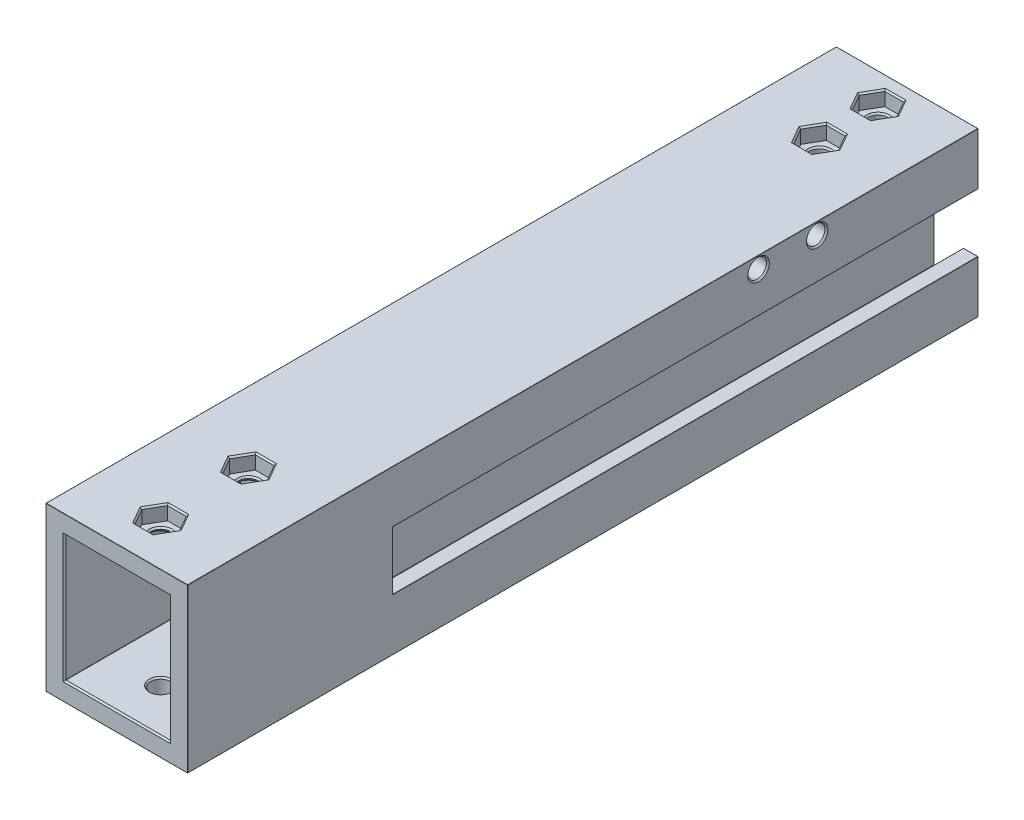
SolidWorks part; units mm, degrees
ref_plane "Front Plane" through (0, 0, 0) normal (0, 0, 1) x (1, 0, 0)
ref_plane "Top Plane" through (0, 0, 0) normal (0, 1, 0) x (1, 0, 0)
ref_plane "Right Plane" through (0, 0, 0) normal (1, 0, 0) x (0, 0, -1)
sketch "Sketch1" plane through (0, 0, 0) normal (0, 0, 1) x (1, 0, 0)
  line L0 (-6.35, -6.35) -> (-6.35, 49.35)
  line L1 (0, 0) -> (35.72, 0) construction
  line L2 (0, 0) -> (0, 43) construction
  line L3 (0, 43) -> (35.72, 43) construction
  line L4 (35.72, 0) -> (35.72, 43) construction
  line L5 (-6.35, 49.35) -> (42.07, 49.35)
  line L6 (42.07, -6.35) -> (42.07, 49.35)
  line L7 (-6.35, -6.35) -> (42.07, -6.35)
  dimension "D1" = 35.72
  dimension "D2" = 43
  dimension "D3" = 6.35
extrude "Boss-Extrude1" add sketch "Sketch1" against normal blind 270
sketch "Sketch2" plane through (0, 0, 0) normal (0, 0, 1) x (1, 0, 0)
  line L0 (35.72, 43) -> (0, 43)
  line L1 (0, 43) -> (0, 0)
  line L2 (0, 0) -> (35.72, 0)
  line L3 (35.72, 0) -> (35.72, 43)
  line L4 (-6.35, -6.35) -> (42.07, -6.35)
  line L5 (42.07, -6.35) -> (42.07, 49.35)
  line L6 (42.07, 49.35) -> (-6.35, 49.35)
  line L7 (-6.35, 49.35) -> (-6.35, -6.35)
  line L8 (-6.35, -6.35) -> (42.07, -6.35) construction
  line L9 (42.07, -6.35) -> (42.07, 49.35) construction
  line L10 (42.07, 49.35) -> (-6.35, 49.35) construction
  line L11 (-6.35, 49.35) -> (-6.35, -6.35) construction
  dimension "D1" = 0
  dimension "D2" = 6.35
extrude "Cut-Extrude1" cut sketch "Sketch2" against normal blind 60
sketch "Sketch3" plane through (0, -6.35, 0) normal (0, -1, 0) x (1, 0, 0)
  line L4 (42.07, 0) -> (-6.35, 0)
  line L5 (-6.35, 0) -> (-6.35, -270)
  line L12 (-6.35, -270) -> (42.07, -270)
  line L13 (42.07, -270) -> (42.07, 0)
  line L14 (42.07, 0) -> (-6.35, 0) construction
  line L15 (-6.35, 0) -> (-6.35, -270) construction
  line L16 (-6.35, -270) -> (42.07, -270) construction
  line L17 (42.07, -270) -> (42.07, 0) construction
  circle A1 centre (17.86, -260) radius 3.3734
  circle A3 centre (17.86, -240) radius 3.3734
  circle A5 centre (17.86, -45) radius 3.3734
  circle A8 centre (17.86, -15) radius 3.3734
  point P3 (17.86, -270)
  point P12 (0, 0)
  dimension "D6" = 6.7469
  dimension "D2" = 10
  dimension "D3" = 20
  dimension "D4" = 15
  dimension "D5" = 30
  dimension "D1" = 0
extrude "Cut-Extrude2" cut sketch "Sketch3" against normal through all
sketch "Sketch8" plane through (0, 0, -270) normal (0, 0, -1) x (-1, 0, 0)
  line L0 (6.35, 21.5) -> (-42.07, 21.5) construction
  line L1 (6.35, 11.5) -> (1.35, 11.5)
  line L2 (1.35, 11.5) -> (1.35, 1.5)
  line L3 (1.35, 1.5) -> (-8.65, 1.5)
  line L4 (-42.07, -6.35) -> (6.35, -6.35)
  line L5 (6.35, -6.35) -> (6.35, 49.35)
  line L6 (6.35, 49.35) -> (-42.07, 49.35)
  line L7 (-42.07, 49.35) -> (-42.07, -6.35)
  line L8 (-42.07, -6.35) -> (6.35, -6.35) construction
  line L9 (6.35, -6.35) -> (6.35, 49.35) construction
  line L10 (6.35, 49.35) -> (-42.07, 49.35) construction
  line L11 (-42.07, 49.35) -> (-42.07, -6.35) construction
  line L12 (-8.65, 1.5) -> (-8.65, 41.5)
  line L13 (6.35, 31.5) -> (1.35, 31.5)
  line L14 (1.35, 31.5) -> (1.35, 41.5)
  line L15 (1.35, 41.5) -> (-8.65, 41.5)
  line L16 (-17.86, -6.35) -> (-17.86, 49.35) construction
  line L17 (-42.07, 11.5) -> (-37.07, 11.5)
  line L18 (-37.07, 11.5) -> (-37.07, 1.5)
  line L19 (-37.07, 1.5) -> (-27.07, 1.5)
  line L20 (-42.07, 31.5) -> (-37.07, 31.5)
  line L21 (-37.07, 41.5) -> (-27.07, 41.5)
  line L22 (-37.07, 31.5) -> (-37.07, 41.5)
  line L23 (-27.07, 1.5) -> (-27.07, 41.5)
  line L24 (6.35, 31.5) -> (6.35, 11.5)
  line L25 (-42.07, 31.5) -> (-42.07, 11.5)
  point P2 (6.35, 21.5)
  point P16 (-8.65, 21.5)
  dimension "D2" = 10
  dimension "D3" = 20
  dimension "D4" = 10
  dimension "D5" = 5
  dimension "D1" = 0
extrude "Cut-Extrude4" cut sketch "Sketch8" against normal blind 200
sketch "Sketch11" plane through (-6.35, 0, 0) normal (-1, 0, 0) x (0, 0, 1)
  circle A0 centre (-195, 45.2313) radius 3.175 construction
  circle A1 centre (-215, 45.2313) radius 3.175 construction
  circle A2 centre (-195, 45.2313) radius 3.175
  circle A3 centre (-215, 45.2313) radius 3.175
extrude "Cut-Extrude5" cut sketch "Sketch11" against normal through all
sketch "Sketch12" plane through (0, 0, -270) normal (0, 0, -1) x (-1, 0, 0)
  line L0 (-42.07, 31.5) -> (-42.07, 11.5) construction
  line L1 (-10.36, 6.5) -> (-25.36, 6.5)
  line L2 (-10.36, 6.5) -> (-10.36, 36.5)
  line L3 (-10.36, 36.5) -> (-25.36, 36.5)
  line L4 (-25.36, 6.5) -> (-25.36, 36.5)
  line L20 (6.35, -6.35) -> (6.35, 11.5)
  line L21 (6.35, 11.5) -> (1.35, 11.5)
  line L22 (1.35, 11.5) -> (1.35, 1.5)
  line L23 (1.35, 1.5) -> (-8.65, 1.5)
  line L24 (-8.65, 1.5) -> (-8.65, 41.5)
  line L25 (-8.65, 41.5) -> (1.35, 41.5)
  line L26 (1.35, 41.5) -> (1.35, 31.5)
  line L27 (1.35, 31.5) -> (6.35, 31.5)
  line L28 (6.35, 31.5) -> (6.35, 49.35)
  line L29 (6.35, 49.35) -> (-42.07, 49.35)
  line L30 (-42.07, 49.35) -> (-42.07, 31.5)
  line L31 (-42.07, 31.5) -> (-37.07, 31.5)
  line L32 (-37.07, 31.5) -> (-37.07, 41.5)
  line L33 (-37.07, 41.5) -> (-27.07, 41.5)
  line L34 (-27.07, 41.5) -> (-27.07, 1.5)
  line L35 (-27.07, 1.5) -> (-37.07, 1.5)
  line L36 (-37.07, 1.5) -> (-37.07, 11.5)
  line L37 (-37.07, 11.5) -> (-42.07, 11.5)
  line L38 (-42.07, 11.5) -> (-42.07, -6.35)
  line L39 (-42.07, -6.35) -> (6.35, -6.35)
  line L40 (6.35, -6.35) -> (6.35, 11.5) construction
  line L41 (6.35, 11.5) -> (1.35, 11.5) construction
  line L42 (1.35, 11.5) -> (1.35, 1.5) construction
  line L43 (1.35, 1.5) -> (-8.65, 1.5) construction
  line L44 (-8.65, 1.5) -> (-8.65, 41.5) construction
  line L45 (-8.65, 41.5) -> (1.35, 41.5) construction
  line L46 (1.35, 41.5) -> (1.35, 31.5) construction
  line L47 (1.35, 31.5) -> (6.35, 31.5) construction
  line L48 (6.35, 31.5) -> (6.35, 49.35) construction
  line L49 (6.35, 49.35) -> (-42.07, 49.35) construction
  line L50 (-42.07, 49.35) -> (-42.07, 31.5) construction
  line L51 (-42.07, 31.5) -> (-37.07, 31.5) construction
  line L52 (-37.07, 31.5) -> (-37.07, 41.5) construction
  line L53 (-37.07, 41.5) -> (-27.07, 41.5) construction
  line L54 (-27.07, 41.5) -> (-27.07, 1.5) construction
  line L55 (-27.07, 1.5) -> (-37.07, 1.5) construction
  line L56 (-37.07, 1.5) -> (-37.07, 11.5) construction
  line L57 (-37.07, 11.5) -> (-42.07, 11.5) construction
  line L58 (-42.07, 11.5) -> (-42.07, -6.35) construction
  line L59 (-42.07, -6.35) -> (6.35, -6.35) construction
  point P10 (-25.36, 21.5)
  point P12 (-17.86, 6.5)
  point P14 (-42.07, 21.5)
  point P16 (-17.86, -6.35)
  dimension "D2" = 30
  dimension "D3" = 15
  dimension "D1" = 0
extrude "Cut-Extrude6" cut sketch "Sketch12" against normal blind 50
sketch "Sketch13" plane through (0, 49.35, 0) normal (0, 1, 0) x (1, 0, 0)
  line L1 (24.2758, 240) -> (21.0679, 245.5563)
  line L2 (21.0679, 245.5563) -> (14.6521, 245.5563)
  line L3 (14.6521, 245.5563) -> (11.4442, 240)
  line L4 (-6.35, 0) -> (42.07, 0)
  line L12 (11.4442, 240) -> (14.6521, 234.4437)
  line L13 (14.6521, 234.4437) -> (21.0679, 234.4437)
  line L14 (21.0679, 234.4437) -> (24.2758, 240)
  line L15 (24.2758, 260) -> (21.0679, 265.5563)
  line L16 (21.0679, 265.5563) -> (14.6521, 265.5562)
  line L17 (14.6521, 265.5562) -> (11.4442, 260)
  line L18 (11.4442, 260) -> (14.6521, 254.4438)
  line L19 (14.6521, 254.4438) -> (21.0679, 254.4438)
  line L20 (21.0679, 254.4438) -> (24.2758, 260)
  line L21 (24.2758, 45) -> (21.0679, 50.5563)
  line L22 (21.0679, 50.5563) -> (14.6521, 50.5563)
  line L23 (14.6521, 50.5563) -> (11.4442, 45)
  line L24 (11.4442, 45) -> (14.6521, 39.4438)
  line L25 (14.6521, 39.4438) -> (21.0679, 39.4438)
  line L26 (21.0679, 39.4438) -> (24.2758, 45)
  line L27 (24.2758, 15) -> (21.0679, 20.5563)
  line L28 (21.0679, 20.5563) -> (14.6521, 20.5563)
  line L29 (14.6521, 20.5563) -> (11.4442, 15)
  line L30 (11.4442, 15) -> (14.6521, 9.4437)
  line L31 (14.6521, 9.4437) -> (21.0679, 9.4438)
  line L32 (21.0679, 9.4438) -> (24.2758, 15)
  line L68 (-6.35, 0) -> (42.07, 0) construction
  line L72 (42.07, 0) -> (42.07, 270)
  line L74 (42.07, 0) -> (42.07, 270) construction
  line L76 (42.07, 270) -> (-6.35, 270)
  line L77 (42.07, 270) -> (-6.35, 270) construction
  line L78 (-6.35, 270) -> (-6.35, 0)
  line L79 (-6.35, 270) -> (-6.35, 0) construction
  circle A0 centre (17.86, 45) radius 3.3734 construction
  circle A2 centre (17.86, 260) radius 3.3734 construction
  circle A4 centre (17.86, 45) radius 3.3734 construction
  circle A6 centre (17.86, 260) radius 3.3734 construction
  circle A8 centre (17.86, 240) radius 5.5563 construction
  circle A9 centre (17.86, 260) radius 5.5563 construction
  circle A10 centre (17.86, 45) radius 5.5563 construction
  circle A11 centre (17.86, 15) radius 5.5562 construction
  circle A12 centre (17.86, 15) radius 3.3734 construction
  circle A13 centre (17.86, 240) radius 3.3734 construction
  circle A14 centre (17.86, 15) radius 3.3734 construction
  circle A15 centre (17.86, 240) radius 3.3734 construction
  point P0 (18.7361, 269.0167)
  point P5 (0, 0)
  point P7 (0, 0)
  point P11 (0, 0)
  point P12 (10.1894, 244.5739)
  point P16 (23.22, 15)
  point P17 (17.86, 234.4437)
  point P46 (17.86, 50.5563)
  point P47 (17.86, 9.4438)
  point P55 (0, 0)
  point P56 (12.5989, 260)
  dimension "D2" = 11.1125
  dimension "D3" = 11.1125
  dimension "D4" = 11.1125
  dimension "D5" = 11.1125
  dimension "D1" = 0
extrude "Cut-Extrude9" cut sketch "Sketch13" against normal blind 5
chamfer "Chamfer1" distance 0.5 angle 45 52 edges at (-6.35, 45.2313, -211.825) (42.07, 45.2313, -211.825) (-6.35, 45.2313, -191.825) (42.07, 45.2313, -191.825) (21.2334, 0, -45) (17.86, -6.35, -48.3734) (35.72, 21.5, 0) (17.86, 0, 0) (17.86, 43, 0) (0, 21.5, 0) (14.4866, 43, -45) (25.36, 21.5, -270) (17.86, 6.5, -270) (10.36, 21.5, -270) (17.86, 36.5, -270) (17.86, -6.35, -263.3734) (21.2334, 6.5, -260) (14.4866, 36.5, -260) (21.2334, 0, -15) (17.86, -6.35, -18.3734) (17.86, -6.35, -243.3734) (21.2334, 6.5, -240) (14.4866, 36.5, -240) (14.4866, 43, -15) (22.6719, 49.35, -242.7781) (22.6719, 49.35, -237.2219) (17.86, 49.35, -234.4437) (13.0481, 49.35, -237.2219) (13.0481, 49.35, -242.7781) (17.86, 49.35, -245.5563) (13.0481, 49.35, -257.2219) (17.86, 49.35, -254.4438) (22.6719, 49.35, -257.2219) (22.6719, 49.35, -262.7781) (17.86, 49.35, -265.5563) (13.0481, 49.35, -262.7781) (17.86, 44.35, -256.6266) (17.86, 44.35, -236.6266) (22.6719, 49.35, -17.7781) (22.6719, 49.35, -12.2219) (17.86, 49.35, -9.4438) (13.0481, 49.35, -12.2219) (13.0481, 49.35, -17.7781) (17.86, 49.35, -20.5563) (22.6719, 49.35, -42.2219) (22.6719, 49.35, -47.7781) (17.86, 49.35, -50.5563) (13.0481, 49.35, -47.7781) (17.86, 49.35, -39.4438) (13.0481, 49.35, -42.2219) (17.86, 44.35, -41.6266) (17.86, 44.35, -11.6266)
fillet "Fillet7" radius 0.1 76 edges at (42.07, 11.5, -170) (39.57, 11.5, -270) (32.07, 1.5, -270) (27.07, 1.5, -170) (27.07, 21.5, -270) (42.07, 31.5, -170) (39.57, 31.5, -270) (27.07, 41.5, -170) (32.07, 41.5, -270) (-1.35, 41.5, -170) (3.65, 41.5, -270) (-1.35, 1.5, -170) (3.65, 1.5, -270) (8.65, 41.5, -170) (8.65, 1.5, -170) (8.65, 21.5, -270) (17.86, 0, -60) (0, 21.5, -60) (17.86, 43, -60) (35.72, 21.5, -60) (17.86, 6.5, -220) (25.36, 21.5, -220) (17.86, 36.5, -220) (10.36, 21.5, -220) (37.07, 11.5, -170) (37.07, 1.5, -170) (37.07, 6.5, -270) (37.07, 41.5, -170) (37.07, 31.5, -170) (37.07, 36.5, -270) (39.57, 31.5, -70) (37.07, 36.5, -70) (32.07, 41.5, -70) (27.07, 21.5, -70) (32.07, 1.5, -70) (37.07, 6.5, -70) (39.57, 11.5, -70) (42.07, 21.5, -70) (-6.35, 31.5, -170) (-1.35, 31.5, -170) (-3.85, 31.5, -270) (-1.35, 11.5, -170) (-6.35, 11.5, -170) (-3.85, 11.5, -270) (-3.85, 11.5, -70) (-1.35, 6.5, -70) (3.65, 1.5, -70) (8.65, 21.5, -70) (3.65, 41.5, -70) (-1.35, 36.5, -70) (-3.85, 31.5, -70) (-6.35, 21.5, -70) (-1.35, 36.5, -270) (42.07, 40.425, -270) (42.07, 2.575, -270) (-1.35, 6.5, -270) (-6.35, 2.575, -270) (-6.35, 40.425, -270) (17.86, 49.35, -270) (17.86, -6.35, -270) (-6.35, -6.35, -135) (42.07, 49.35, -135) (42.07, -6.35, -135) (-6.35, 49.35, -135) (-6.35, 21.5, 0) (17.86, 49.35, 0) (17.86, -6.35, 0) (42.07, 21.5, 0) (0, 0, -30.25) (0, 43, -30.25) (35.72, 0, -30.25) (35.72, 43, -30.25) (10.36, 36.5, -244.75) (25.36, 36.5, -244.75) (10.36, 6.5, -244.75) (25.36, 6.5, -244.75)
